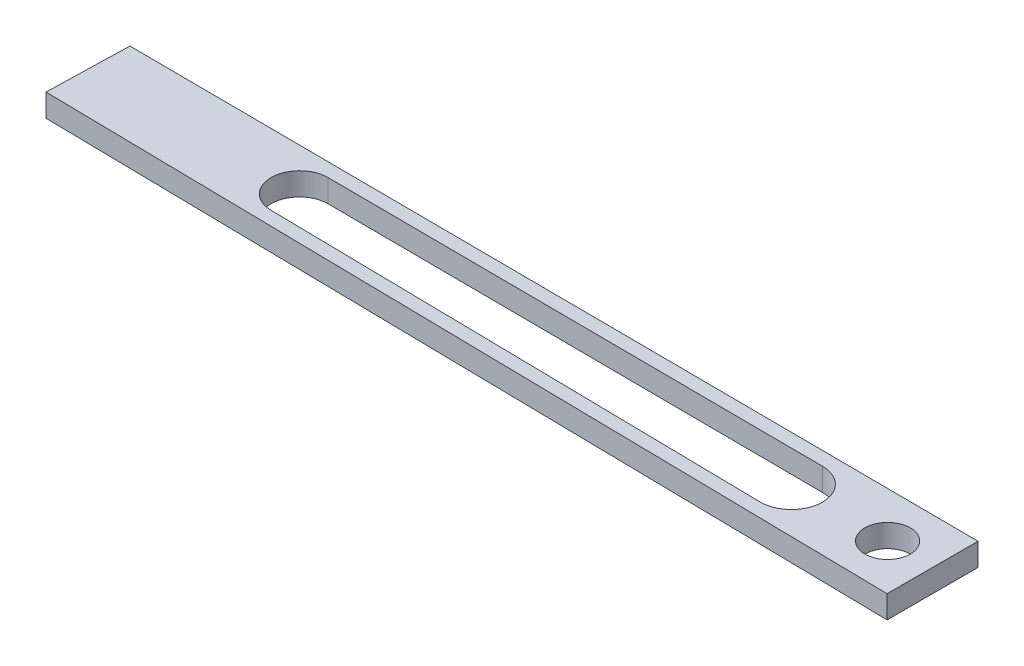
SolidWorks part; units mm, degrees
note: The reader was unsure of these and kept them because the rebuilt part matched: shared geometry of "Sketch1<7>", "Sketch1<9>", "Sketch1<11>".
ref_plane "Front Plane" through (0, 0, 0) normal (0, 0, 1) x (1, 0, 0)
ref_plane "Top Plane" through (0, 0, 0) normal (0, 1, 0) x (1, 0, 0)
ref_plane "Right Plane" through (0, 0, 0) normal (1, 0, 0) x (0, 0, -1)
sketch "Sketch1" plane through (0, 0, 0) normal (0, 1, 0) x (1, 0, 0)
  line L29 (-90, -42.8477) -> (-90.4749, -60.8477)
  line L30 (-90.4749, -60.8477) -> (97.6498, -63.907)
  line L31 (97.6498, -63.907) -> (97.6498, -43.907)
  line L32 (97.6498, -43.907) -> (-90, -42.8477)
  line L33 (-90.2374, -51.8477) -> (97.6498, -53.907) construction
  line L34 (-70.5369, -45.1306) -> (-70.6129, -52.0628) construction
  line L35 (-72.4369, -45.1306) -> (-72.4369, -48.4306)
  line L36 (-68.6369, -58.6306) -> (-68.6369, -54.7806)
  line L37 (-87.4316, -50.3933) -> (-72.4369, -48.4306)
  line L38 (-87.4316, -53.3679) -> (-72.4369, -55.3306)
  line L39 (-55.6416, -50.393) -> (-68.6369, -48.9806)
  line L40 (-55.6416, -54.0564) -> (-68.6369, -54.7806)
  line L41 (-68.6369, -48.9806) -> (-68.6369, -45.1306)
  line L42 (-72.4369, -55.3306) -> (-72.4369, -58.6306)
  line L43 (-52.8407, -43.0575) -> (-52.8407, -61.4597)
  line L48 (-49.8407, -43.0575) -> (-49.8407, -43.0744)
  line L50 (66.1534, -60.3944) -> (-43.272, -58.6141)
  line L51 (-49.8407, -43.0575) -> (-49.8407, -61.4597) construction
  line L52 (-43.1351, -46.1123) -> (66.3032, -46.7308)
  arc A10 (-87.4316, -50.3933) -> (-87.4316, -53.3679) centre (-87.2369, -51.8806) ccw
  arc A11 (-55.6416, -54.0564) -> (-55.6416, -50.393) centre (-55.8407, -52.2247) ccw
  arc A12 (-72.4369, -58.6306) -> (-68.6369, -58.6306) centre (-70.5369, -58.6306) ccw
  arc A13 (-68.6369, -45.1306) -> (-72.4369, -45.1306) centre (-70.5369, -45.1306) ccw
  circle A14 centre (-70.6377, -52.1822) radius 1.275
  circle A15 centre (-70.6377, -52.1822) radius 2.35
  circle A16 centre (87.6498, -53.7974) radius 5
  arc A17 (66.1534, -60.3944) -> (66.3032, -46.7308) centre (66.2645, -53.563) ccw
  arc A18 (-43.1351, -46.1123) -> (-43.272, -58.6141) centre (-43.1704, -52.3636) ccw
  point P1 (0, 0)
  point P42 (-53.9982, -52.2247)
  point P45 (-88.7369, -51.8806)
  point P65 (94.6498, -46.8901)
  point P66 (-87.0785, -45.8643)
  point P67 (-87.396, -57.8974)
  point P68 (94.6498, -60.8578)
  dimension "D8" = 10
  dimension "D9" = 10
  dimension "D6" = 3
  dimension "D7" = 3
extrude "Boss-Extrude1" add sketch "Sketch1" along normal blind 5 contours L32 L29 L30 L31
extrude "Cut-Extrude1" cut sketch "Sketch1<7>" along normal blind 1.5 contours L37 L35 A13 L41 L39 A11 L40 L36 A12 L42 L38 A10
sketch "Sketch1<7>" plane through (0, 0, 0) normal (0, 1, 0) x (1, 0, 0) same geometry as "Sketch1"
extrude "Cut-Extrude2" cut sketch "Sketch1<9>" along normal through all contours L52 A18 L50 A17
sketch "Sketch1<9>" plane through (0, 0, 0) normal (0, 1, 0) x (1, 0, 0) same geometry as "Sketch1"
extrude "Cut-Extrude4" cut sketch "Sketch1<11>" along normal through all contours A16
sketch "Sketch1<11>" plane through (0, 0, 0) normal (0, 1, 0) x (1, 0, 0) same geometry as "Sketch1"
